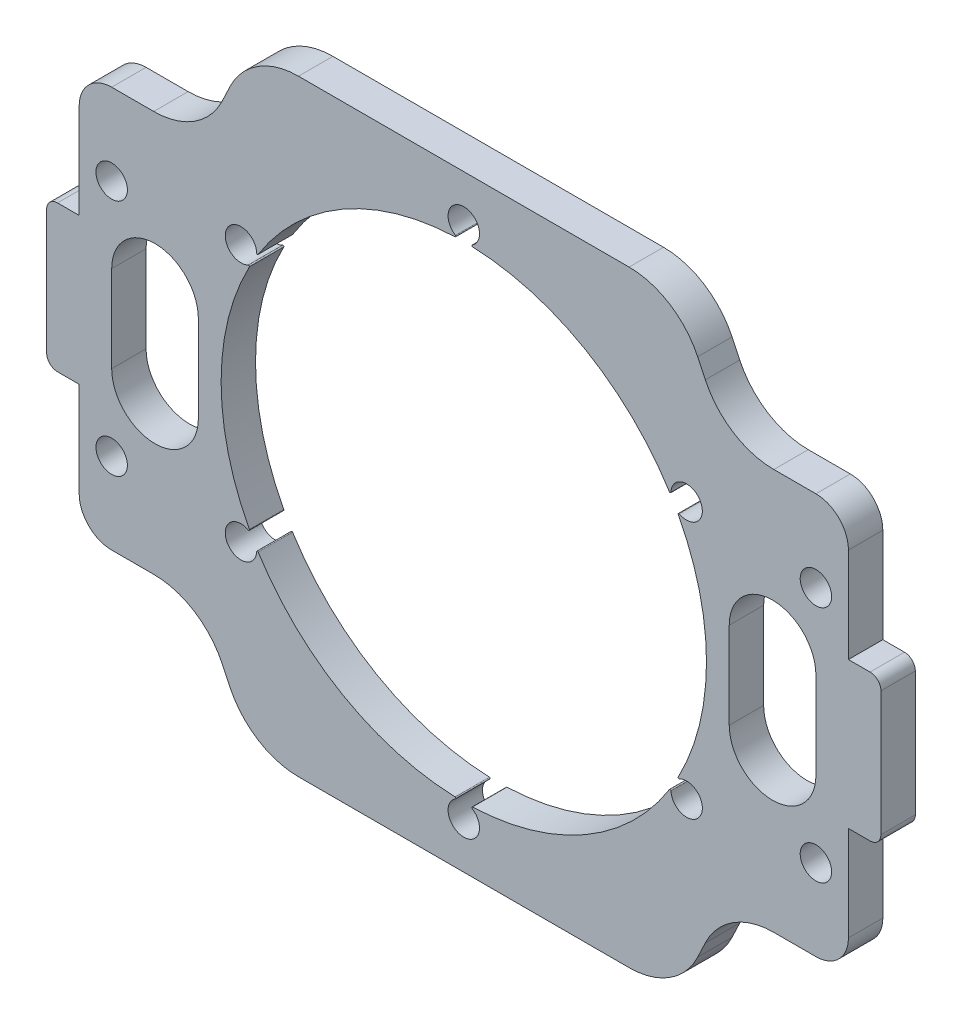
SolidWorks part; units mm, degrees
material "AISI 1035 Steel (SS)"
ref_plane "Front Plane" through (0, 0, 0) normal (0, 0, 1) x (1, 0, 0)
ref_plane "Top Plane" through (0, 0, 0) normal (0, 1, 0) x (1, 0, 0)
ref_plane "Right Plane" through (0, 0, 0) normal (1, 0, 0) x (0, 0, -1)
sketch "Sketch1" plane through (0, 0, 0) normal (0, 0, 1) x (1, 0, 0)
  line L1 (-35.5, 28) -> (35.5, 28)
  line L2 (-35.5, 28) -> (-35.5, -28)
  line L3 (-35.5, -28) -> (35.5, -28)
  line L4 (35.5, 28) -> (35.5, -28)
  line L5 (-35.5, 28) -> (35.5, -28) construction
  line L6 (-35.5, -28) -> (35.5, 28) construction
  circle A0 centre (0, 0) radius 22.4
  point P0 (0, 0)
  dimension "D3" = 44.8
  dimension "D1" = 56
  dimension "14" = 71
extrude "Boss-Extrude1" add sketch "Sketch1" along normal blind 3.175
sketch "Sketch3" plane through (0, 0, 3.175) normal (0, 0, 1) x (1, 0, 0)
  circle A0 centre (0, 0) radius 23.75 construction
  circle A1 centre (0, 23.75) radius 1.45
  circle A2 centre (20.5681, 11.875) radius 1.45
  circle A3 centre (20.5681, -11.875) radius 1.45
  circle A4 centre (0, -23.75) radius 1.45
  circle A5 centre (-20.5681, -11.875) radius 1.45
  circle A6 centre (-20.5681, 11.875) radius 1.45
  point P18 (0, 0)
  dimension "D1" = 2.9
  dimension "D3" = 47.5
  dimension "D2" = 6
extrude "Cut-Extrude2" cut sketch "Sketch3" against normal through all
sketch "Sketch11" plane through (0, 0, 3.175) normal (0, 0, 1) x (1, 0, 0)
  line L1 (35.5, 28) -> (-35.5, 28) construction
  line L2 (-24.188, 18.5) -> (-35.5, 18.5)
  line L3 (-35.5, 28) -> (-35.5, -28) construction
  line L4 (-35.5, 18.5) -> (-35.5, 28)
  line L5 (-35.5, 28) -> (-19.688, 28)
  line L6 (0, 39.643) -> (0, -36.5597) construction
  line L7 (35.5, 28) -> (19.688, 28)
  line L8 (35.5, 18.5) -> (35.5, 28)
  line L9 (24.188, 18.5) -> (35.5, 18.5)
  line L10 (19.688, 28) -> (24.188, 18.5)
  line L11 (-5.9465, 0) -> (11.012, 0) construction
  line L12 (19.688, -28) -> (24.188, -18.5)
  line L13 (24.188, -18.5) -> (35.5, -18.5)
  line L14 (35.5, -18.5) -> (35.5, -28)
  line L15 (35.5, -28) -> (19.688, -28)
  line L16 (-35.5, -28) -> (-19.688, -28)
  line L17 (-35.5, -18.5) -> (-35.5, -28)
  line L18 (-24.188, -18.5) -> (-35.5, -18.5)
  line L19 (-19.688, -28) -> (-24.188, -18.5)
  line L20 (-24.188, 18.5) -> (-19.688, 28)
  dimension "D1" = 4.5
  dimension "D2" = 37
extrude "Cut-Extrude7" cut sketch "Sketch11" against normal through all
sketch "Sketch12" plane through (0, 0, 3.175) normal (0, 0, 1) x (1, 0, 0)
  line L0 (0, 16.2679) -> (0, -10.1222) construction
  line L1 (-32.5, 11) -> (-32.5, -11) construction
  line L2 (-35.5, 18.5) -> (-35.5, -18.5) construction
  circle A0 centre (-32.5, 11) radius 1.45
  circle A1 centre (-32.5, -11) radius 1.45
  circle A2 centre (32.5, -11) radius 1.45
  circle A3 centre (32.5, 11) radius 1.45
  point P5 (-32.5, 0)
  dimension "D2" = 2.9
  dimension "D1" = 22
  dimension "D3" = 3
extrude "Cut-Extrude8" cut sketch "Sketch12" against normal through all both and the other way through all
sketch "Sketch15" plane through (0, 0, 0) normal (0, 0, -1) x (-1, 0, 0)
  line L0 (0, 37.4812) -> (0, -9.8909) construction
  line L1 (-35.5, -18.5) -> (-35.5, 18.5) construction
  line L2 (-38.5, 6.75) -> (-35.5, 6.75)
  line L3 (-38.5, 6.75) -> (-38.5, -6.75)
  line L4 (-38.5, -6.75) -> (-35.5, -6.75)
  line L5 (-35.5, 6.75) -> (-35.5, -6.75)
  line L6 (35.5, 6.75) -> (35.5, -6.75)
  line L7 (38.5, -6.75) -> (35.5, -6.75)
  line L8 (38.5, 6.75) -> (38.5, -6.75)
  line L9 (38.5, 6.75) -> (35.5, 6.75)
  point P9 (-35.5, 0)
  dimension "D1" = 3
  dimension "D2" = 13.5
extrude "Boss-Extrude3" add sketch "Sketch15" against normal up to surface (3.175 mm away) up to face at (33.95, 11, 3.175)
fillet "Fillet3" radius 7 8 edges at (19.688, -28, 1.5875) (24.188, -18.5, 1.5875) (-19.688, -28, 1.5875) (-24.188, -18.5, 1.5875) (19.688, 28, 1.5875) (24.188, 18.5, 1.5875) (-19.688, 28, 1.5875) (-24.188, 18.5, 1.5875)
fillet "Fillet4" radius 3 4 edges at (35.5, -18.5, 1.5875) (35.5, 18.5, 1.5875) (-35.5, 18.5, 1.5875) (-35.5, -18.5, 1.5875)
sketch "Sketch10" plane through (0, 0, 3.175) normal (0, 0, 1) x (1, 0, 0)
  line L0 (-28.5, 4) -> (-28.5, -4) construction
  line L1 (-24.5, 4) -> (-24.5, -4)
  line L2 (-32.5, 4) -> (-32.5, -4)
  line L3 (0, 38.1014) -> (0, -40.9645) construction
  line L4 (28.5, 4) -> (28.5, -4) construction
  line L5 (24.5, 4) -> (24.5, -4)
  line L6 (32.5, 4) -> (32.5, -4)
  arc A0 (-24.5, 4) -> (-32.5, 4) centre (-28.5, 4) ccw
  arc A1 (-32.5, -4) -> (-24.5, -4) centre (-28.5, -4) ccw
  arc A2 (24.5, 4) -> (32.5, 4) centre (28.5, 4) cw
  arc A3 (32.5, -4) -> (24.5, -4) centre (28.5, -4) cw
  point P2 (-28.5, 0)
  point P12 (28.5, 0)
  dimension "D1" = 8
  dimension "D2" = 32.5
  dimension "D3" = 8
extrude "Cut-Extrude6" cut sketch "Sketch10" against normal through all
fillet "Fillet5" radius 1 4 edges at (-38.5, -6.75, 1.5875) (-38.5, 6.75, 1.5875) (38.5, -6.75, 1.5875) (38.5, 6.75, 1.5875)
fillet "Fillet6" radius 0.075 12 edges at (19.6508, -10.752, 1.5875) (19.1369, -11.6421, 1.5875) (-0.5139, -22.3941, 1.5875) (0.5139, -22.3941, 1.5875) (-19.6508, -10.752, 1.5875) (-19.1369, -11.6421, 1.5875) (-19.1369, 11.6421, 1.5875) (-19.6508, 10.752, 1.5875) (0.5139, 22.3941, 1.5875) (-0.5139, 22.3941, 1.5875) (19.6508, 10.752, 1.5875) (19.1369, 11.6421, 1.5875)
